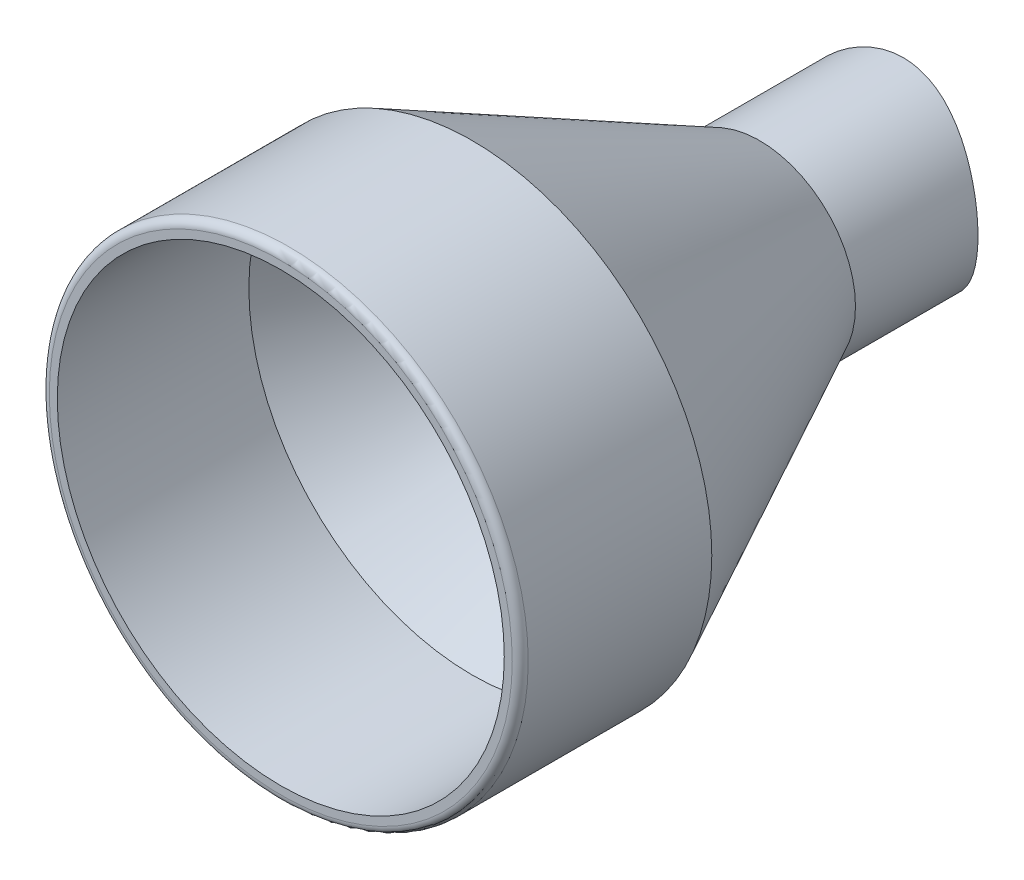
SolidWorks part; units mm, degrees
ref_plane "Front Plane" through (0, 0, 0) normal (0, 0, 1) x (1, 0, 0)
ref_plane "Top Plane" through (0, 0, 0) normal (0, 1, 0) x (1, 0, 0)
ref_plane "Right Plane" through (0, 0, 0) normal (1, 0, 0) x (0, 0, -1)
sketch "Sketch1" plane through (0, 0, 0) normal (0, 0, 1) x (1, 0, 0)
  circle A0 centre (0, 0) radius 15
  circle A1 centre (0, 0) radius 14
  dimension "D1" = 30
  dimension "D2" = 1
extrude "Boss-Extrude1" add sketch "Sketch1" along normal blind 12
sketch "Sketch2" plane through (0, 0, 0) normal (0, 0, -1) x (-1, 0, 0)
  circle A0 centre (0, 0) radius 15 construction
  point P0 (0, 0)
  point P1 (0, 15)
sketch "Sketch4" plane through (0, 0, 12) normal (0, 0, 1) x (1, 0, 0)
  point P0 (0, 15)
ref_plane "Plane1" through (0, 0, 0) normal (1, 0, 0) x (0, 0, -1)
sketch "Sketch5" plane through (0, 0, 0) normal (1, 0, 0) x (0, 0, -1)
  line L0 (0, 0) -> (30, 0) construction
  line L3 (18, 6) -> (0, 15)
  line L4 (0, -15) -> (0, 15) construction
  line L5 (0, 15) -> (0, 14)
  line L6 (0, 14) -> (18, 5)
  line L7 (18, 5) -> (18, 6)
  line L10 (18, 6) -> (27, 6)
  line L11 (18, 6) -> (18, 5)
  line L12 (18, 5) -> (27, 5)
  line L13 (27, 6) -> (27, 5)
  dimension "D1" = 18
  dimension "D2" = 9
  dimension "D3" = 5
fillet "Fillet1" radius 0.5 1 edges at (15, 0, 12)
revolve "Revolve1" add sketch "Sketch5" angle 360 about L0 region at (0, 10, -9) region at (0, 5.5, -22.5)
sketch "Sketch6" plane through (0, 0, 0) normal (1, 0, 0) x (0, 0, -1)
  line L2 (27, 6) -> (27, -6) construction
  circle A0 centre (39.9253, 0) radius 14.25
  point P5 (27, 0)
  dimension "D1" = 28.5
extrude "Cut-Extrude1" cut sketch "Sketch6" against normal blind 10 and the other way blind 10
sketch "Sketch7" plane through (0, 0, 12) normal (0, 0, 1) x (1, 0, 0)
  line L1 (-4, -1) -> (-6, -1)
  line L2 (-4, -1) -> (-4, 1)
  line L3 (-4, 1) -> (-6, 1)
  line L4 (-6, -1) -> (-6, 1)
  line L5 (-4, -1) -> (-6, 1) construction
  line L6 (-4, 1) -> (-6, -1) construction
  line L7 (4, -1) -> (6, -1)
  line L8 (4, -1) -> (4, 1)
  line L9 (4, 1) -> (6, 1)
  line L10 (6, -1) -> (6, 1)
  line L11 (4, -1) -> (6, 1) construction
  line L12 (4, 1) -> (6, -1) construction
  circle A0 centre (0, 0) radius 6 construction
  circle A1 centre (0, 0) radius 6
  point P0 (-5, 0)
  point P5 (5, 0)
  dimension "D1" = 2
  dimension "D2" = 2
  dimension "D3" = 2
  dimension "D4" = 2
extrude "Boss-Extrude2" add sketch "Sketch7" against normal blind 4 from offset 30 contours L3 A1 L1 L2 | A1 L9 L8 L7 region at (-4.9862, 0, 12) region at (4.9862, 0, 12) offset against normal yes
chamfer "Chamfer1" distance 1 angle 45 2 edges at (-4, 0, -22) (4, 0, -22)
